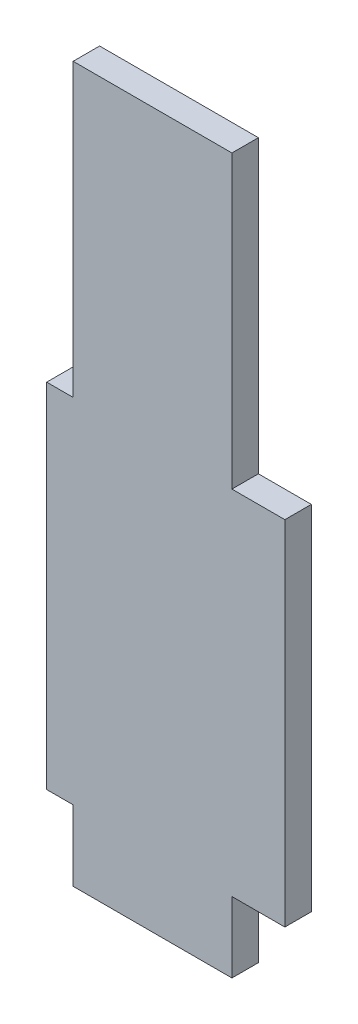
SolidWorks part; units mm, degrees
ref_plane "Front Plane" through (0, 0, 0) normal (0, 0, 1) x (1, 0, 0)
ref_plane "Top Plane" through (0, 0, 0) normal (0, 1, 0) x (1, 0, 0)
ref_plane "Right Plane" through (0, 0, 0) normal (1, 0, 0) x (0, 0, -1)
sketch "Sketch1" plane through (0, 0, 0) normal (0, 0, 1) x (1, 0, 0)
  line L1 (-18, 61) -> (0, 61)
  line L2 (-18, 61) -> (-18, 0)
  line L3 (-18, 0) -> (0, 0)
  line L4 (0, 61) -> (0, 0)
  dimension "D1" = 61
  dimension "D2" = 18
extrude "Base Shape" add sketch "Sketch1" along normal blind 3
sketch "Sketch2" plane through (0, 0, 3) normal (0, 0, 1) x (1, 0, 0)
  line L0 (-18, 61) -> (-18, 0) construction
  line L1 (-18, 8) -> (-21, 8)
  line L2 (-18, 8) -> (-18, 48)
  line L3 (-18, 48) -> (-21, 48)
  line L4 (-21, 8) -> (-21, 48)
  line L5 (0, 0) -> (0, 61) construction
  line L6 (0, 8) -> (6, 8)
  line L7 (0, 8) -> (0, 48)
  line L8 (0, 48) -> (6, 48)
  line L9 (6, 8) -> (6, 48)
  line L10 (-18, 0) -> (0, 0) construction
  line M11 (0, 0) -> (0, 61)
  dimension "D1" = 8
  dimension "D2" = 40
  dimension "D3" = 3
  dimension "D4" = 6
extrude "Fingers" add sketch "Sketch2" against normal up to surface (3 mm away) contours L6 L9 L8 M11 | L4 L3 L2 L1 region at (3, 28, 3) up to face at (-9, 30.5, 0)
sketch "Sketch3" plane through (0, 61, 0) normal (0, 1, 0) x (1, 0, 0)
  line L1 (-18, 0) -> (0, 0)
  line L2 (-18, 0) -> (-18, -3)
  line L3 (-18, -3) -> (0, -3)
  line L4 (0, 0) -> (0, -3)
extrude "Boss-Extrude1" add sketch "Sketch3" along normal blind 20
